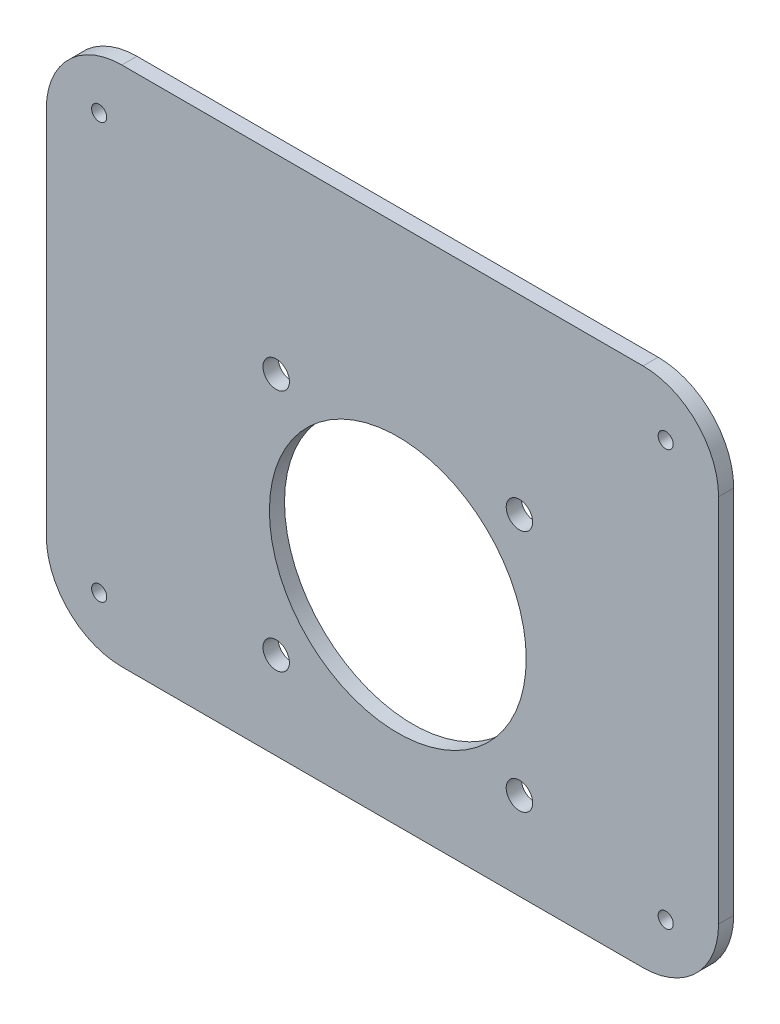
SolidWorks part; units mm, degrees
ref_plane "前视基准面" through (0, 0, 0) normal (0, 0, 1) x (1, 0, 0)
ref_plane "上视基准面" through (0, 0, 0) normal (0, 1, 0) x (1, 0, 0)
ref_plane "右视基准面" through (0, 0, 0) normal (1, 0, 0) x (0, 0, -1)
sketch "草图1" plane through (0, 0, 0) normal (0, 0, 1) x (1, 0, 0)
  line L0 (10, 0) -> (10, -10)
  line L1 (10, 0) -> (79, 0)
  line L2 (0, -10) -> (0, -59)
  line L3 (10, -69) -> (79, -69)
  line L4 (89, -10) -> (89, -59)
  line L5 (10, -10) -> (0, -10)
  line L6 (44.5, 0) -> (44.5, -69) construction
  line L7 (0, -34.5) -> (89, -34.5)
  line L8 (79, -10) -> (89, -10)
  line L9 (79, 0) -> (79, -10)
  line L10 (79, -59) -> (89, -59)
  line L11 (79, -69) -> (79, -59)
  line L12 (10, -59) -> (0, -59)
  line L13 (10, -69) -> (10, -59)
  arc A0 (79, 0) -> (89, -10) centre (79, -10) cw
  arc A1 (0, -59) -> (10, -69) centre (10, -59) ccw
  arc A2 (79, -69) -> (89, -59) centre (79, -59) ccw
  arc A3 (10, 0) -> (0, -10) centre (10, -10) ccw
  circle A4 centre (7, -7) radius 1
  circle A5 centre (82, -7) radius 1
  circle A6 centre (82, -62) radius 1
  circle A7 centre (7, -62) radius 1
  point P7 (89, 0)
  point P10 (0, -69)
  point P15 (0, 0)
  dimension "D3" = 10
  dimension "D5" = 3
  dimension "D6" = 2
  dimension "D1" = 89
  dimension "D2" = 69
  dimension "D4" = 3
extrude "凸台-拉伸1" add sketch "草图1" against normal blind 2 contours L6 L1 L0 L5 L2 L7 | L1 L6 L7 L4 L8 L9 | L6 L7 L2 L12 L13 L3 | L7 L6 L3 L11 L10 L4 | L0 A3 L5 A4 | A0 L9 L8 A5 | L12 A1 L13 A7 | L11 A2 L10 A6 region at (23.4519, -18.1035, 0) region at (5.704, -5.704, 0) region at (65.5481, -18.1035, 0) region at (83.296, -5.704, 0) region at (65.5481, -50.8965, 0) region at (23.4519, -50.8965, 0) region at (5.704, -63.296, 0) region at (83.296, -63.296, 0)
sketch "草图2" plane through (0, 0, 0) normal (0, 0, 1) x (1, 0, 0)
  circle A0 centre (30.4339, -25.2308) radius 1.75
  circle A1 centre (62.6339, -25.2308) radius 1.75
  circle A2 centre (46.5339, -41.3308) radius 17
  circle A3 centre (30.4339, -57.4308) radius 1.75
  circle A4 centre (62.6339, -57.4308) radius 1.75
extrude "切除-拉伸1" cut sketch "草图2" against normal up to next
